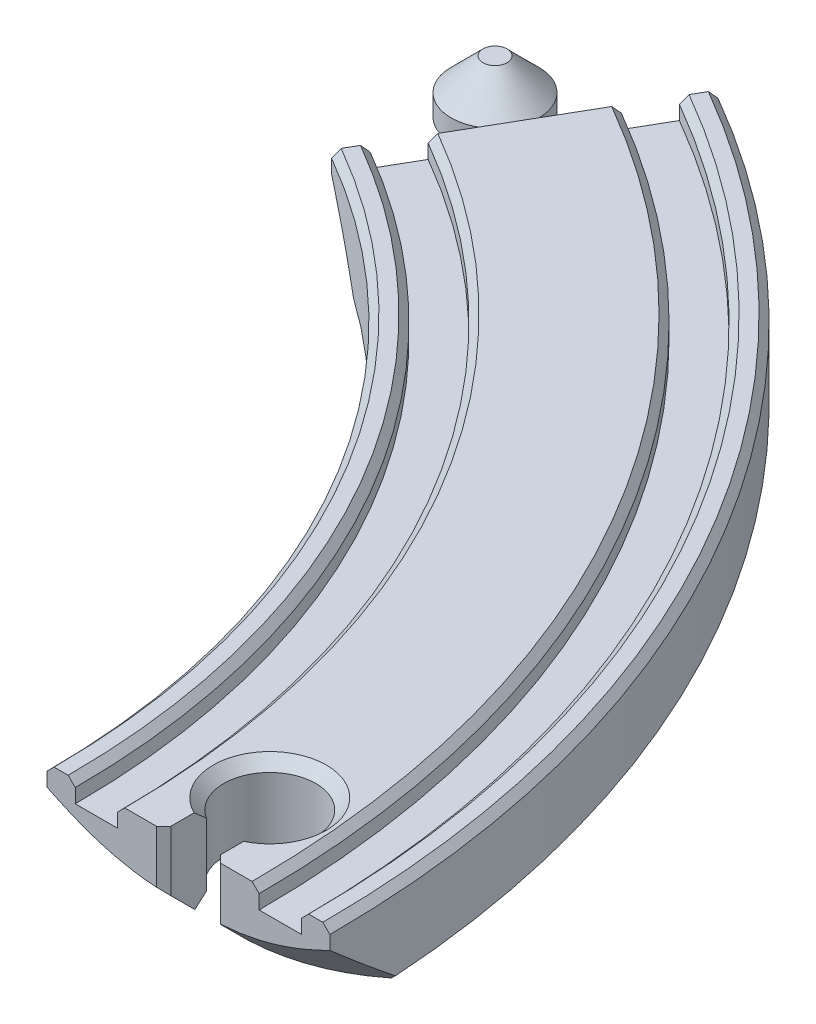
SolidWorks part; units mm, degrees
ref_plane "Front Plane" through (0, 0, 0) normal (0, 0, 1) x (1, 0, 0)
ref_plane "Top Plane" through (0, 0, 0) normal (0, 1, 0) x (1, 0, 0)
ref_plane "Right Plane" through (0, 0, 0) normal (1, 0, 0) x (0, 0, -1)
sketch "Sketch2" plane through (0, 0, 0) normal (0, 0, 1) x (1, 0, 0)
  line L0 (-20, 0) -> (20, 0)
  line L1 (20, 0) -> (20, 12)
  line L2 (20, 12) -> (16, 12)
  line L3 (16, 12) -> (16, 9)
  line L4 (16, 9) -> (10, 9)
  line L5 (10, 9) -> (10, 12)
  line L6 (10, 12) -> (-10, 12)
  line L7 (-10, 12) -> (-10, 9)
  line L8 (-10, 9) -> (-16, 9)
  line L9 (-16, 9) -> (-16, 12)
  line L10 (-16, 12) -> (-20, 12)
  line L11 (-20, 12) -> (-20, 0)
  line L12 (-129.9038, 0) -> (-129.9038, 12)
  point P4 (0, 0)
  dimension "D1" = 40
  dimension "D2" = 12
  dimension "D3" = 3
  dimension "D4" = 4
  dimension "D5" = 6
  dimension "D6" = 129.9038
revolve "Revolve1" add sketch "Sketch2" angle 60 about L12 region at (0, 5.6351, 0)
sketch "Sketch3" plane through (0, 12, 0) normal (0, 1, 0) x (1, 0, 0)
  line L0 (10, 0) -> (-10, 0) construction
  line L2 (-3.5, 0) -> (3.5, 0)
  line L3 (-3.5, 0) -> (-3.5, 11.5)
  line L4 (-3.5, 11.5) -> (3.5, 11.5)
  line L5 (3.5, 0) -> (3.5, 11.5)
  line L6 (-3.5, 0) -> (3.5, 11.5) construction
  line L7 (-3.5, 11.5) -> (3.5, 0) construction
  circle A0 centre (0, 11.5) radius 6.5
  point P4 (0, 5.75)
  point P10 (0, 0)
  line M6 (-10, 0) -> (10, 0)
  dimension "D1" = 13
  dimension "D2" = 11.5
  dimension "D3" = 7
extrude "Cut-Extrude1" cut sketch "Sketch3" against normal through all contours L5 A0 L3 L4 | L3 A0 L5 L4 | A0 L3 L5 M6 region at (0, 12, -2.6732) region at (0, 12, -12.9919) region at (0, 12, -8.4074)
sketch "Sketch4" plane through (0, 12, 0) normal (0, 1, 0) x (1, 0, 0)
  line L0 (-63.4519, 115.0981) -> (-66.4519, 109.9019)
  line L1 (-63.4519, 115.0981) -> (-73.4112, 120.8481)
  line L2 (-66.4519, 109.9019) -> (-76.4112, 115.6519)
  line L3 (-73.4112, 120.8481) -> (-76.4112, 115.6519)
  line L4 (-59.9519, 121.1603) -> (-69.9519, 103.8397) construction
  circle A0 centre (-74.9112, 118.25) radius 6.2
  point P8 (0, 0)
  point P9 (-64.9519, 112.5)
  line M6 (-59.9519, 121.1603) -> (-69.9519, 103.8397)
  dimension "D1" = 12.4
  dimension "D2" = 6
  dimension "D3" = 11.5
extrude "Boss-Extrude1" add sketch "Sketch4" against normal up to surface (12 mm away) contours L1 A0 L2 L3 | L2 A0 L1 L3 region at (-72.3315, 12, -116.7606) region at (-75.9935, 12, -118.8749) up to face at (-12.4699, 0, -33.3033)
extrude "Boss-Extrude2" add sketch "Sketch4<3>" against normal blind 7.5 contours A0 L2 L1 M6 region at (-67.3597, 12, -113.8902)
sketch "Sketch4<3>" plane through (0, 12, 0) normal (0, 1, 0) x (1, 0, 0) same geometry as "Sketch4"
extrude "Cut-Extrude2" cut sketch "Sketch4<5>" against normal blind 4.5 contours A0 L2 L1 M6 region at (-67.3597, 12, -113.8902)
sketch "Sketch4<5>" plane through (0, 12, 0) normal (0, 1, 0) x (1, 0, 0) same geometry as "Sketch4"
chamfer "Chamfer2" distance 4.5 angle 45 1 edges at (-81.1112, 12, -118.25)
chamfer "Chamfer5" distance 3.5 distance2 4.5 1 edges at (-74.9112, 0, -124.45) first distance on face at (-74.9112, 0, -124.45)
chamfer "Chamfer3" distance 1.5 angle 45 2 edges at (0, 0, -18) (0, 12, -18)
sketch "Sketch17" plane through (30.976, 0, -53.6519) normal (-0.5, 0, 0.866) x (0.866, 0, 0.5)
  line L0 (-118.5741, 10.5741) -> (-118.5741, 0)
  line L1 (-118.5741, 0) -> (-108, 0)
  line L2 (-108, 0) -> (-118.5741, 10.5741)
  line L4 (-83, -1.2652) -> (-83, 10.5741) construction
  point P8 (0, 0)
  dimension "D1" = 25
revolve "Cut-Revolve1" cut sketch "Sketch17" angle 90 about L4
ref_plane "Plane1" through (32.476, 0, -56.25) normal (-0.5, 0, 0.866) x (0.866, 0, 0.5)
mirror "Mirror1" about plane through (32.476, 0, -56.25) normal (-0.5, 0, 0.866) of "Cut-Revolve1"
chamfer "Chamfer4" distance 4.5 angle 45 1 edges at (-64.9519, 0, -112.5)
ref_plane "Plane2" through (-32.476, 0, -56.25) normal (-0.5, 0, -0.866) x (-0.866, 0, 0.5)
mirror "Mirror4" about plane through (-32.476, 0, -56.25) normal (-0.5, 0, -0.866) of "Cut-Revolve1", "Mirror1"
chamfer "Chamfer1" distance 1 angle 45 10 edges at (-0.0833, 12, -74.9519) (-3.5474, 12, -72.9519) (-8.7436, 12, -69.9519) (-26.0641, 12, -59.9519) (-31.2602, 12, -56.9519) (-34.7243, 12, -54.9519) (-0.0833, 0, -74.9519) (-34.7243, 0, -54.9519) (3.5, 8.2521, 0) (-3.5, 8.2521, 0)
